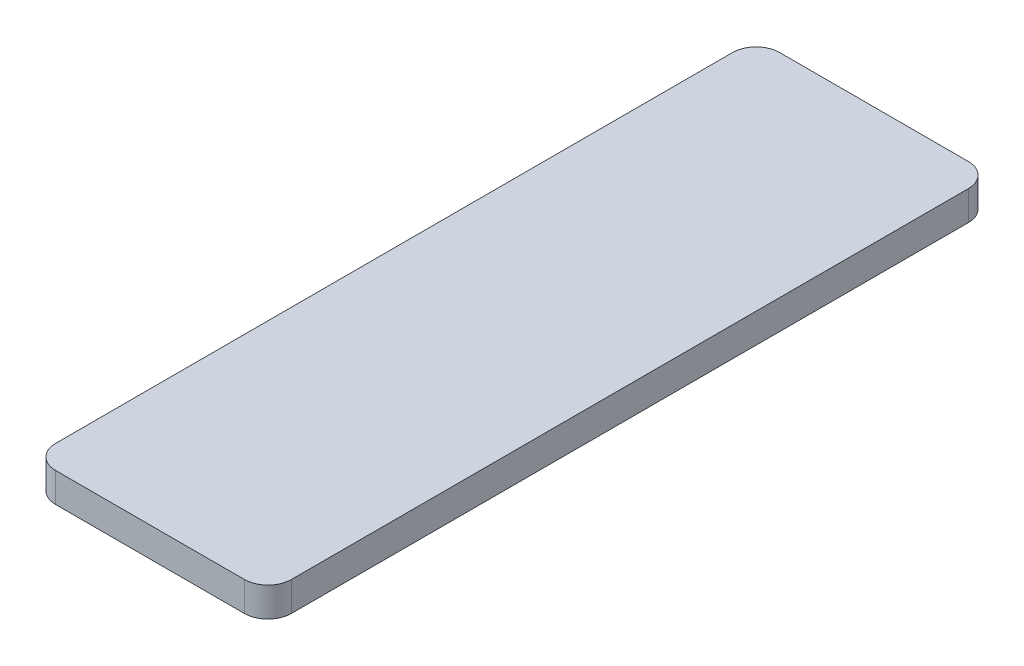
SolidWorks part; units mm, degrees
material "Acrylic (Medium-high impact)"
ref_plane "Front Plane" through (0, 0, 0) normal (0, 0, 1) x (1, 0, 0)
ref_plane "Top Plane" through (0, 0, 0) normal (0, 1, 0) x (1, 0, 0)
ref_plane "Right Plane" through (0, 0, 0) normal (1, 0, 0) x (0, 0, -1)
ref_plane "Plane1" through (0, 0, 0) normal (0, 1, 0) x (1, 0, 0)
sketch "Sketch1" plane through (0, 0, 0) normal (0, 1, 0) x (1, 0, 0)
  line L1 (0, 0) -> (25.4, 0)
  line L2 (0, 0) -> (0, 78)
  line L3 (0, 78) -> (25.4, 78)
  line L4 (25.4, 0) -> (25.4, 78)
  dimension "D1" = 25.4
  dimension "D2" = 78
extrude "Boss-Extrude1" add sketch "Sketch1" along normal blind 3.175
fillet "Fillet1" radius 2.54 4 edges at (25.4, 1.5875, 0) (0, 1.5875, 0) (25.4, 1.5875, -78) (0, 1.5875, -78)
